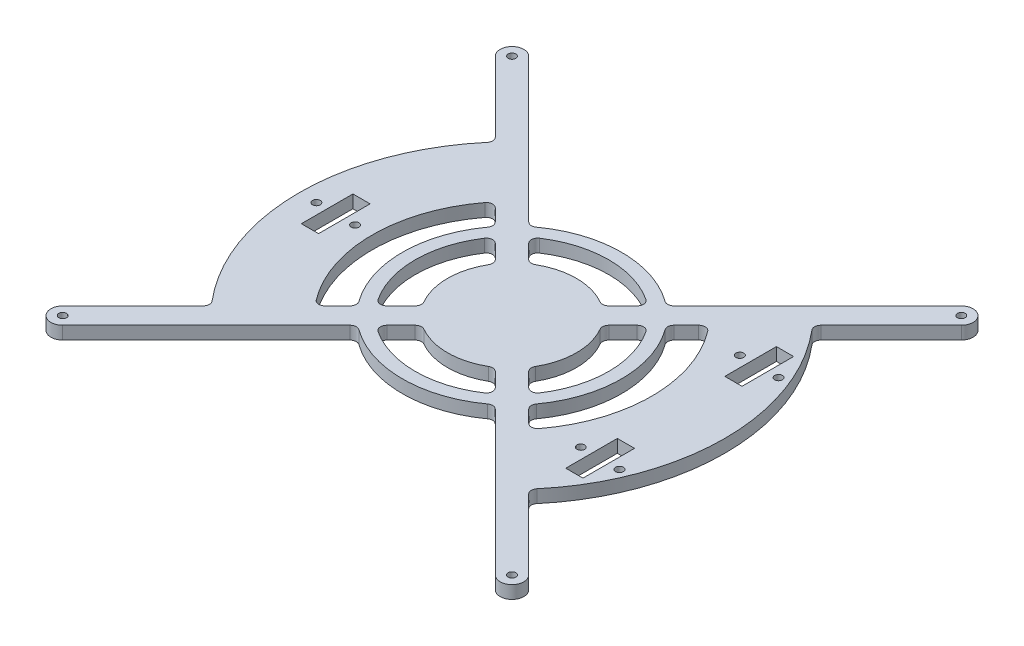
SolidWorks part; units mm, degrees
ref_plane "Front Plane" through (0, 0, 0) normal (0, 0, 1) x (1, 0, 0)
ref_plane "Top Plane" through (0, 0, 0) normal (0, 1, 0) x (1, 0, 0)
ref_plane "Right Plane" through (0, 0, 0) normal (1, 0, 0) x (0, 0, -1)
sketch "Sketch1" plane through (0, 0, 0) normal (0, 1, 0) x (1, 0, 0)
  line L0 (-110, -110) -> (110, 110) construction
  line L1 (-110, 110) -> (110, 110)
  line L2 (-110, 110) -> (-110, -110)
  line L3 (-110, -110) -> (110, -110)
  line L4 (110, 110) -> (110, -110)
  line L5 (-82, 110) -> (-82, -110) construction
  line L6 (78, 25) -> (78, -25) construction
  line L7 (0, 110) -> (0, -110) construction
  line L8 (-78, 0) -> (-73, 0) construction
  line L9 (0, 0) -> (73, 0) construction
  line L10 (-73, 0) -> (0, 0) construction
  line L11 (-86, 12) -> (-78, 12)
  line L12 (-86, 12) -> (-86, -12)
  line L13 (-86, -12) -> (-78, -12)
  line L14 (-78, 12) -> (-78, -12)
  line L15 (73, 0) -> (78, 0) construction
  line L16 (-86, 0) -> (-91, 0) construction
  line L17 (82, 37) -> (87, 37) construction
  line L18 (74, 49) -> (82, 49)
  line L19 (74, 49) -> (74, 25)
  line L20 (74, 25) -> (82, 25)
  line L21 (82, 49) -> (82, 25)
  line L22 (74, -25) -> (82, -25)
  line L23 (74, -25) -> (74, -49)
  line L24 (74, -49) -> (82, -49)
  line L25 (82, -25) -> (82, -49)
  line L26 (74, 37) -> (69, 37) construction
  line L27 (74, -37) -> (69, -37) construction
  line L28 (82, -37) -> (87, -37) construction
  circle A0 centre (-104.5, 104.5) radius 1.8
  circle A1 centre (104.5, 104.5) radius 1.8
  circle A2 centre (104.5, -104.5) radius 1.8
  circle A3 centre (-104.5, -104.5) radius 1.8
  circle A4 centre (-73, 0) radius 1.8
  circle A5 centre (-91, 0) radius 1.8
  circle A6 centre (87, 37) radius 1.8
  circle A7 centre (69, 37) radius 1.8
  circle A8 centre (87, -37) radius 1.8
  circle A9 centre (69, -37) radius 1.8
  point P26 (-82, 12)
  dimension "D3" = 3.6
  dimension "D4" = 5.5
  dimension "D5" = 5.5
  dimension "D9" = 160
  dimension "D10" = 209
  dimension "D1" = 220
  dimension "D2" = 50
  dimension "D6" = 24
  dimension "D7" = 8
  dimension "D8" = 5
extrude "Boss-Extrude1" add sketch "Sketch1" along normal mid plane 6
sketch "Sketch2" plane through (0, -3, 0) normal (0, -1, 0) x (1, 0, 0)
  line L0 (-104.5, 104.5) -> (104.5, -104.5) construction
  line L1 (-110, 110) -> (110, 110)
  line L2 (-110, 110) -> (-110, -110)
  line L3 (-110, -110) -> (110, -110)
  line L4 (110, 110) -> (110, -110)
  line L5 (104.5, 104.5) -> (-104.5, -104.5) construction
  line L6 (-100.6109, 108.3891) -> (-108.3891, 100.6109)
  line L7 (-108.3891, 100.6109) -> (-24.7427, 16.9646)
  line L8 (-100.6109, 108.3891) -> (-16.9646, 24.7427)
  line L9 (-24.7427, 16.9646) -> (-16.9646, 24.7427)
  line L10 (-108.3891, -100.6109) -> (-100.6109, -108.3891)
  line L11 (-100.6109, -108.3891) -> (-16.9646, -24.7427)
  line L12 (-16.9646, -24.7427) -> (-24.7427, -16.9646)
  line L13 (-24.7427, -16.9646) -> (-108.3891, -100.6109)
  line L14 (-91, 0) -> (-99, 0) construction
  line L15 (-73, 0) -> (-65, 0) construction
  line L16 (100.6109, -108.3891) -> (108.3891, -100.6109)
  line L17 (108.3891, -100.6109) -> (24.7427, -16.9646)
  line L18 (24.7427, -16.9646) -> (16.9646, -24.7427)
  line L19 (16.9646, -24.7427) -> (100.6109, -108.3891)
  line L20 (100.6109, 108.3891) -> (108.3891, 100.6109)
  line L21 (108.3891, 100.6109) -> (24.7427, 16.9646)
  line L22 (24.7427, 16.9646) -> (16.9646, 24.7427)
  line L23 (16.9646, 24.7427) -> (100.6109, 108.3891)
  circle A0 centre (-104.5, 104.5) radius 5.5
  circle A1 centre (0, 0) radius 99
  circle A2 centre (0, 0) radius 65
  circle A3 centre (-104.5, -104.5) radius 5.5
  circle A4 centre (0, 0) radius 30
  circle A5 centre (104.5, 104.5) radius 5.5
  circle A6 centre (104.5, -104.5) radius 5.5
  circle A7 centre (0, 0) radius 51
  circle A8 centre (0, 0) radius 45
  point P22 (-104.5, 104.5)
  point P27 (-104.5, -104.5)
  point P44 (104.5, -104.5)
  point P50 (104.5, 104.5)
  line M27 (-110, 110) -> (-110, -110)
  line M28 (-110, -110) -> (110, -110)
  line M29 (110, -110) -> (110, 110)
  line M30 (110, 110) -> (-110, 110)
  dimension "D1" = 11
  dimension "D3" = 8
  dimension "D4" = 11
  dimension "D6" = 60
  dimension "D7" = 6
  dimension "D8" = 90
  dimension "D2" = 11
  dimension "D5" = 11
extrude "Cut-Extrude1" cut sketch "Sketch2" against normal blind 10 contours A3 L13 A1 L7 A0 L2 | A6 L4 A5 L21 A1 L17 | A0 L1 M27 | A3 M27 M28 | A6 M28 M29 | A5 L4 M30 | A2 L23 A1 L8 | A5 L1 A0 L8 A1 L23 | A6 L19 A1 L11 A3 L3 | A2 L11 A1 L19 | A7 L23 A2 L8 | A7 L7 A2 L13 | A7 L11 A2 L19 | A7 L17 A2 L21 | L11 A8 L19 A4 | L7 A8 L13 A4 | L23 A8 L8 A4 | L17 A8 L21 A4 region at (-108.7715, -3, 108.7715) region at (0, -3, 107.8789) region at (-109.7773, -3, 102.3141) region at (108.7715, -3, 108.7715) region at (-108.7715, -3, -108.7715) region at (107.8789, -3, 0) region at (0, -3, 76.2855) region at (-102.3141, -3, -109.7773) region at (108.7715, -3, -108.7715) region at (0, -3, 53.7892) region at (-53.7892, -3, 0) region at (0, -3, -76.2855) region at (53.7892, -3, 0) region at (0, -3, 35.5609) region at (0, -3, -53.7892) region at (-35.5609, -3, 0) region at (35.5609, -3, 0) region at (0, -3, -35.5609)
fillet "Fillet1" radius 3 32 edges at (-73.7845, 0, -66.0064) (-73.7845, 0, 66.0064) (-49.6862, 0, -41.908) (-49.6862, 0, 41.908) (-39.7412, 0, 31.963) (-31.963, 0, -39.7412) (-39.7412, 0, -31.963) (-24.7427, 0, -16.9646) (-24.7427, 0, 16.9646) (-35.4703, 0, 27.6922) (-35.4703, 0, -27.6922) (-27.6922, 0, -35.4703) (27.6922, 0, -35.4703) (-16.9646, 0, -24.7427) (16.9646, 0, -24.7427) (31.963, 0, -39.7412) (73.7845, 0, 66.0064) (73.7845, 0, -66.0064) (49.6862, 0, 41.908) (49.6862, 0, -41.908) (39.7412, 0, -31.963) (24.7427, 0, -16.9646) (35.4703, 0, -27.6922) (24.7427, 0, 16.9646) (16.9646, 0, 24.7427) (-16.9646, 0, 24.7427) (35.4703, 0, 27.6922) (39.7412, 0, 31.963) (27.6922, 0, 35.4703) (31.963, 0, 39.7412) (-27.6922, 0, 35.4703) (-31.963, 0, 39.7412)
